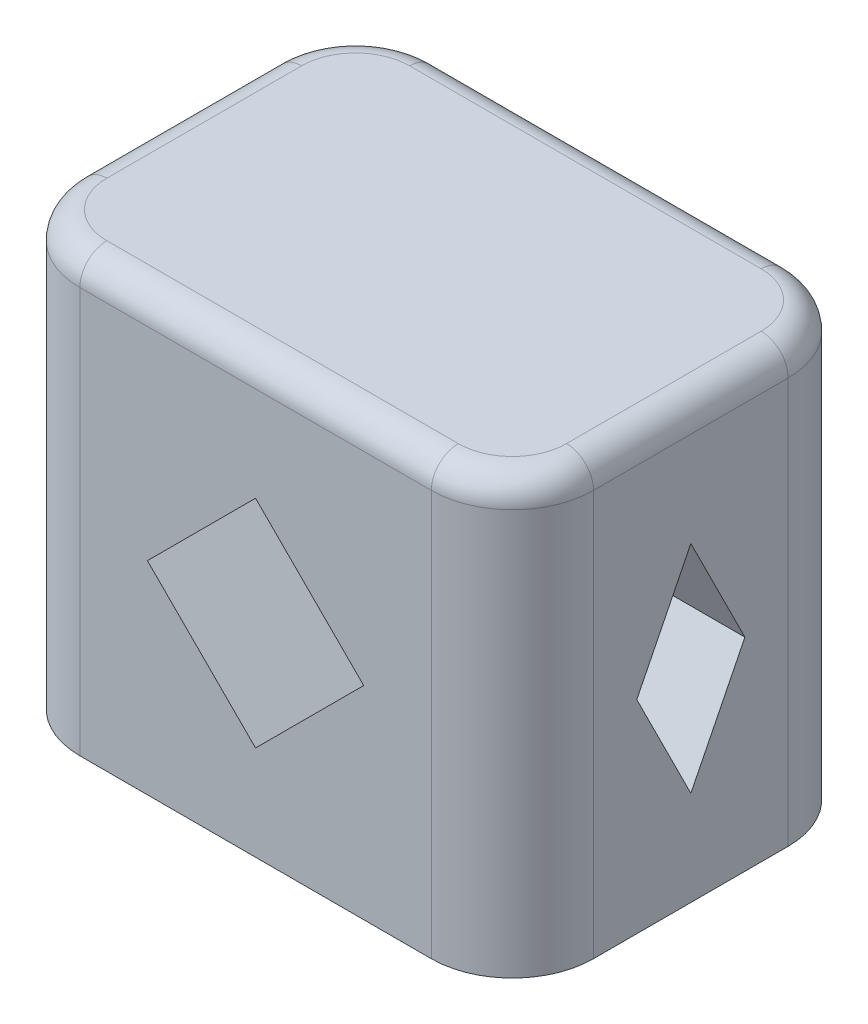
SolidWorks part; units mm, degrees
ref_plane "Front Plane" through (0, 0, 0) normal (0, 0, 1) x (1, 0, 0)
ref_plane "Top Plane" through (0, 0, 0) normal (0, 1, 0) x (1, 0, 0)
ref_plane "Right Plane" through (0, 0, 0) normal (1, 0, 0) x (0, 0, -1)
sketch "Sketch1" plane through (0, 0, 0) normal (0, 1, 0) x (1, 0, 0)
  line L0 (-53.975, 6.35) -> (6.35, 6.35)
  line L5 (6.35, 6.35) -> (6.35, -35.56)
  line L6 (6.35, -35.56) -> (-53.975, -35.56)
  line L7 (-53.975, -35.56) -> (-53.975, 6.35)
extrude "Boss-Extrude1" add sketch "Sketch1" along normal blind 50.8
sketch "Sketch2" plane through (0, 0, -6.35) normal (0, 0, 1) x (1, 0, 0)
  line L0 (-36.5125, 31.75) -> (-53.975, 31.75) construction
  line L1 (-53.975, 50.8) -> (-53.975, 0) construction
  line L2 (-11.1125, 31.75) -> (6.35, 31.75) construction
  line L3 (6.35, 50.8) -> (6.35, 0) construction
  line L4 (-53.975, 50.8) -> (6.35, 50.8) construction
  circle A0 centre (-36.5125, 31.75) radius 1.905
  circle A1 centre (-11.1125, 31.75) radius 1.905
  dimension "D3" = 3.81
  dimension "D1" = 25.4
  dimension "D2" = 19.05
extrude "Cut-Extrude1" cut sketch "Sketch2" along normal blind 9.525
fillet "Fillet1" [suppressed] radius 6.35
ref_plane "Plane2" through (0, 40.64, 0) normal (0, 1, 0) x (1, 0, 0)
ref_plane "Plane3" through (-23.8125, 0, 0) normal (1, 0, 0) x (0, 0, -1)
sketch "Sketch9" plane through (-23.8125, 0, 0) normal (1, 0, 0) x (0, 0, -1)
  line L0 (1.3517, 50.8) -> (1.3517, 0)
  line L2 (-35.56, 50.8) -> (6.35, 50.8) construction
  line L3 (-35.56, 0) -> (6.35, 0) construction
  line L5 (1.3517, 0) -> (-23.505, 0.8272)
  line L6 (1.3517, 50.8) -> (-30.5988, 50.8)
  line L8 (-30.5988, 50.8) -> (-30.5988, 10.9242)
  line L9 (-25.1322, 3.957) -> (-28.1184, 6.9433)
  line L10 (-23.505, -0.043) -> (-23.505, -53.2333) construction
  line L11 (0.5579, 19.6933) -> (0.5579, 93.7927) construction
  line L12 (-29.805, 92.4549) -> (-29.805, 10.9433) construction
  arc A0 (-23.505, 0.8272) -> (-25.1322, 3.957) centre (-26.7729, 1.1161) ccw
  arc A1 (-30.5988, 10.9242) -> (-28.1184, 6.9433) centre (-11.7056, 19.9325) ccw
  dimension "D1" = 0.7937
  dimension "D2" = 0.7937
extrude "Cut-Extrude7" cut sketch "Sketch9" against normal offset from surface 0.7937 and the other way offset from surface 0.7937 rebuild error yes offset beyond the face yes
chamfer "Chamfer2" distance 7.46 angle 33 rebuild error yes
sketch "Sketch10" plane through (0, 0, 0) normal (0, 1, 0) x (1, 0, 0)
  line L0 (-47.369, -30.8528) -> (-39.5465, -30.8528)
  line L1 (-47.2426, -30.5988) -> (-0.3824, -30.5988) construction
  line L2 (-39.5465, -30.8528) -> (-47.369, -25.7728)
  line L3 (-47.9545, -3.4119) -> (-47.2426, -30.5988) construction
  line L4 (-47.369, -25.7728) -> (-47.369, -30.8528)
  line L7 (-0.256, -30.8528) -> (-0.256, -25.7728)
  line L8 (0.3295, -3.4119) -> (-0.3824, -30.5988) construction
  line L9 (-0.256, -25.7728) -> (-8.0785, -30.8528)
  line L10 (-8.0785, -30.8528) -> (-0.256, -30.8528)
  dimension "D1" = 33
  dimension "D2" = 5.08
  dimension "D3" = 33
  dimension "D4" = 0.254
extrude "Boss-Extrude2" add sketch "Sketch10" along normal up to surface (50.8 mm away) up to face at (-23.8125, 50.8, 14.605)
fillet "Fillet3" radius 9.525 4 edges at (6.35, 25.4, 35.56) (6.35, 25.4, -6.35) (-53.975, 25.4, -6.35) (-53.975, 25.4, 35.56)
fillet "Fillet4" radius 3.175 8 edges at (-51.1852, 50.8, -3.5602) (-23.8125, 50.8, -6.35) (3.5602, 50.8, -3.5602) (6.35, 50.8, 14.605) (3.5602, 50.8, 32.7702) (-23.8125, 50.8, 35.56) (-51.1852, 50.8, 32.7702) (-53.975, 50.8, 14.605)
sketch "Sketch12" plane through (0, 0, 35.56) normal (0, 0, 1) x (1, 0, 0)
  line L0 (-23.8125, 11.1125) -> (-23.8125, 36.5125) construction
  line L1 (-36.5125, 23.8125) -> (-11.1125, 23.8125) construction
  line L2 (-36.5125, 23.8125) -> (-23.8125, 36.5125)
  line L3 (-23.8125, 36.5125) -> (-11.1125, 23.8125)
  line L4 (-11.1125, 23.8125) -> (-23.8125, 11.1125)
  line L5 (-23.8125, 11.1125) -> (-36.5125, 23.8125)
  line L6 (-44.45, 47.625) -> (-44.45, 0) construction
  line L7 (-3.175, 47.625) -> (-44.45, 47.625) construction
  point P0 (-44.45, 23.8125)
  point P5 (-23.8125, 23.8125)
  point P6 (-23.8125, 23.8125)
  point P7 (-23.8125, 47.625)
  dimension "D1" = 25.4
  dimension "D2" = 25.4
extrude "Cut-Extrude8" cut sketch "Sketch12" against normal up to next and the other way through all
sketch "Sketch13" plane through (-53.975, 0, 0) normal (-1, 0, 0) x (0, 0, 1)
  line L0 (3.175, 47.625) -> (3.175, 0) construction
  line L1 (26.035, 47.625) -> (3.175, 47.625) construction
  line L2 (14.605, 11.1125) -> (14.605, 36.5125) construction
  line L3 (8.255, 23.8125) -> (20.955, 23.8125) construction
  line L4 (8.255, 23.8125) -> (14.605, 36.5125)
  line L5 (14.605, 36.5125) -> (20.955, 23.8125)
  line L6 (20.955, 23.8125) -> (14.605, 11.1125)
  line L7 (14.605, 11.1125) -> (8.255, 23.8125)
  point P0 (3.175, 23.8125)
  point P1 (14.605, 47.625)
  point P9 (14.605, 23.8125)
  point P12 (14.605, 23.8125)
  dimension "D1" = 25.4
  dimension "D2" = 12.7
extrude "Cut-Extrude9" cut sketch "Sketch13" against normal through all both and the other way through all
